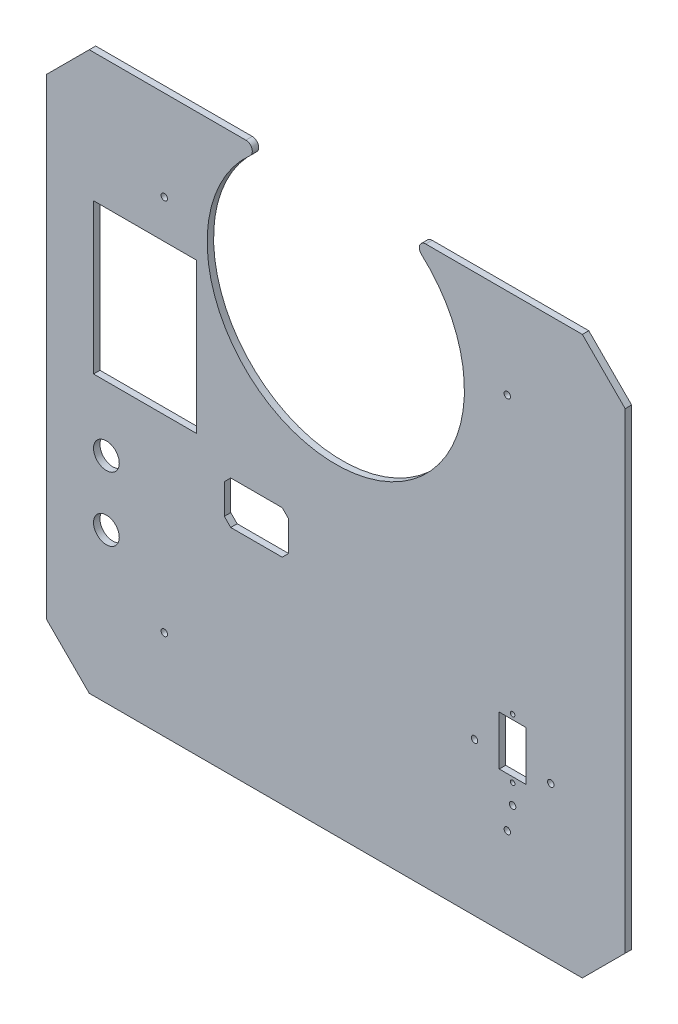
SolidWorks part; units mm, degrees
ref_plane "前视基准面" through (0, 0, 0) normal (0, 0, 1) x (1, 0, 0)
ref_plane "上视基准面" through (0, 0, 0) normal (0, 1, 0) x (1, 0, 0)
ref_plane "右视基准面" through (0, 0, 0) normal (1, 0, 0) x (0, 0, -1)
other "Configuration Table"
sketch "草图1" plane through (0, 0, 0) normal (0, 0, 1) x (1, 0, 0)
  line L1 (-135, -130) -> (135, -130)
  line L2 (-135, -130) -> (-135, 130)
  line L3 (-135, 130) -> (135, 130)
  line L4 (135, -130) -> (135, 130)
  line L5 (-135, -130) -> (135, 130) construction
  line L6 (-135, 130) -> (135, -130) construction
  point P0 (0, 0)
  dimension "D1" = 270
  dimension "D2" = 260
extrude "凸台-拉伸1" add sketch "草图1" along normal blind 3
sketch "草图2" plane through (0, 0, 3) normal (0, 0, 1) x (1, 0, 0)
  line L1 (135, 130) -> (-135, 130) construction
  line L4 (-50, 130) -> (50, 130)
  point P3 (0, 80)
  dimension "D1" = 100
chamfer "倒角2" distance 20 angle 45 4 edges at (-135, -130, 1.5) (135, -130, 1.5) (135, 130, 1.5) (-135, 130, 1.5)
sketch "草图3" plane through (0, 0, 3) normal (0, 0, 1) x (1, 0, 0)
  line L1 (88.75, -69.5) -> (76.25, -69.5)
  line L2 (88.75, -69.5) -> (88.75, -37.5)
  line L3 (88.75, -37.5) -> (76.25, -37.5)
  line L4 (76.25, -69.5) -> (76.25, -37.5)
sketch "草图4" plane through (0, 0, 3) normal (0, 0, 1) x (1, 0, 0)
  circle A0 centre (0, 80) radius 60
  dimension "D1" = 120
extrude "切除-拉伸1" cut sketch "草图4" against normal blind 10
fillet "圆角1" radius 3 2 edges at (-33.1662, 130, 1.5) (33.1662, 130, 1.5)
sketch "草图5" plane through (0, 0, 0) normal (0, 0, -1) x (-1, 0, 0)
  line L1 (-88.75, -41.9445) -> (-76.25, -41.9445)
  line L2 (-88.75, -41.9445) -> (-88.75, -64.9471)
  line L3 (-88.75, -64.9471) -> (-76.25, -64.9471)
  line L4 (-76.25, -41.9445) -> (-76.25, -64.9471)
  circle A0 centre (-64.7, -58.75) radius 1.5
  circle A1 centre (-100.3, -58.75) radius 1.5
  circle A2 centre (-82.5, -76.55) radius 1.5
  circle A3 centre (-82.5, -39.65) radius 1.05
  circle A4 centre (-82.5, -67.35) radius 1.05
  dimension "D1" = 2.1
  dimension "D2" = 2.1
extrude "切除-拉伸2" cut sketch "草图5" against normal blind 10
sketch "草图6" plane through (0, 0, 0) normal (0, 0, -1) x (-1, 0, 0)
  line L6 (65, 0) -> (113, 0)
  line L7 (65, 0) -> (65, 70)
  line L8 (65, 70) -> (113, 70)
  line L9 (113, 0) -> (113, 70)
extrude "切除-拉伸3" cut sketch "草图6" against normal blind 0.1
sketch "草图7" plane through (0, 0, 0) normal (0, 0, -1) x (-1, 0, 0)
  line L0 (65, 70) -> (113, 70) construction
  line L1 (65, 0) -> (115, 0)
  line L2 (65, 0) -> (65, 70)
  line L3 (65, 70) -> (115, 70)
  line L4 (115, 0) -> (115, 70)
sketch "草图8" plane through (0, 0, 3) normal (0, 0, 1) x (1, 0, 0)
  line L0 (-135, 110) -> (-135, -110) construction
  line L1 (-65, 70) -> (-113, 70) construction
  circle A0 centre (-107, 40) radius 6
  circle A1 centre (-107, 10) radius 6
  dimension "D1" = 28
  dimension "D2" = 28
  dimension "D3" = 12
  dimension "D4" = 12
  dimension "D5" = 30
  dimension "D6" = 30
sketch "草图10" plane through (0, 0, 0) normal (0, 0, -1) x (-1, 0, 0)
  line L0 (113, 0) -> (113, 70) construction
  line L1 (65, 70) -> (113, 70)
  line L2 (65, 70) -> (65, 0)
  line L3 (65, 0) -> (113, 0)
  line L4 (113, 70) -> (113, 0)
extrude "切除-拉伸4" cut sketch "草图10" against normal through all
sketch "草图11" plane through (0, 0, 3) normal (0, 0, 1) x (1, 0, 0)
  circle A0 centre (-107, -30) radius 6 construction
  circle A1 centre (-107, -30) radius 6
  circle A2 centre (-107, -60) radius 6 construction
  circle A3 centre (-107, -60) radius 6
extrude "切除-拉伸5" cut sketch "草图11" against normal through all
sketch "草图13" plane through (0, 0, 0) normal (0, 0, -1) x (-1, 0, 0)
  circle A0 centre (80, 88) radius 1.5
  circle A1 centre (80, -88) radius 1.5
  circle A2 centre (-80, -88) radius 1.5
  circle A3 centre (-80, 88) radius 1.5
extrude "切除-拉伸6" cut sketch "草图13" against normal through all
sketch "草图15" plane through (0, 0, 0) normal (0, 0, -1) x (-1, 0, 0)
  line L0 (-42, -30) -> (42, -30) construction
  line L1 (22, -30) -> (52, -30)
  line L2 (22, -30) -> (22, -10)
  line L3 (22, -10) -> (52, -10)
  line L4 (52, -30) -> (52, -10)
  line L5 (52, -20) -> (52, 20) construction
  dimension "D1" = 30
  dimension "D2" = 20
extrude "切除-拉伸8" cut sketch "草图15" against normal through all
chamfer "倒角4" distance 3 angle 45 4 edges at (-22, -10, 1.5) (-52, -10, 1.5) (-52, -30, 1.5) (-22, -30, 1.5)
